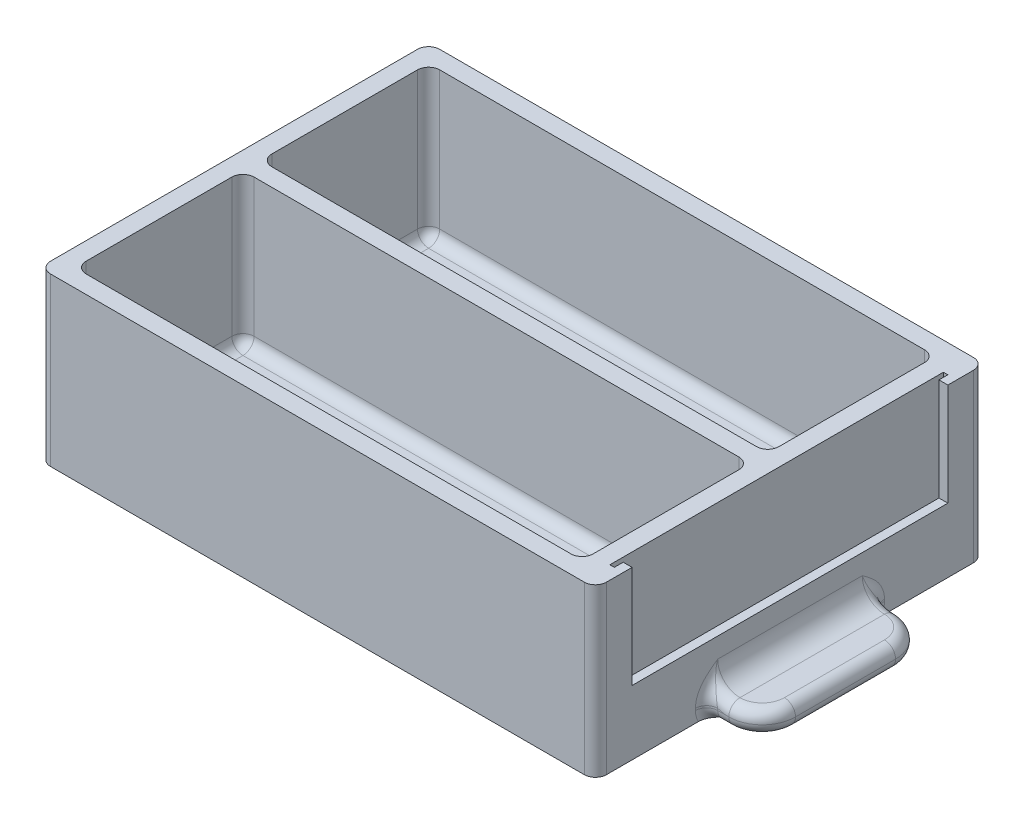
SolidWorks part; units mm, degrees
ref_plane "Спереди" through (0, 0, 0) normal (0, 0, 1) x (1, 0, 0)
ref_plane "Сверху" through (0, 0, 0) normal (0, 1, 0) x (1, 0, 0)
ref_plane "Справа" through (0, 0, 0) normal (1, 0, 0) x (0, 0, -1)
sketch "Эскиз1" plane through (0, 0, 0) normal (0, 1, 0) x (1, 0, 0)
  line L1 (-25, -17.5) -> (25, -17.5)
  line L2 (-25, -17.5) -> (-25, 17.5)
  line L3 (-25, 17.5) -> (25, 17.5)
  line L4 (25, -17.5) -> (25, 17.5)
  line L5 (-25, -17.5) -> (25, 17.5) construction
  line L6 (-25, 17.5) -> (25, -17.5) construction
  line L7 (-23.4, 15.9) -> (22.2, 15.9)
  line L8 (-23.4, 15.9) -> (-23.4, -15.9)
  line L9 (-23.4, -15.9) -> (22.2, -15.9)
  line L10 (22.2, 15.9) -> (22.2, -15.9)
  line L11 (-23.4, -0.8) -> (22.2, -0.8)
  line L12 (-23.4, -0.8) -> (-23.4, 0.8)
  line L13 (-23.4, 0.8) -> (22.2, 0.8)
  line L14 (22.2, -0.8) -> (22.2, 0.8)
  line L15 (-23.4, -0.8) -> (22.2, 0.8) construction
  line L16 (-23.4, 0.8) -> (22.2, -0.8) construction
  point P0 (0, 0)
  point P10 (-0.6, 0)
  dimension "D1" = 50
  dimension "D2" = 35
  dimension "D3" = 1.6
  dimension "D4" = 1.6
  dimension "D5" = 1.6
  dimension "D6" = 2.8
  dimension "D7" = 1.6
extrude "Бобышка-Вытянуть1" add sketch "Эскиз1" along normal blind 15 contours L1 L4 L3 L2
extrude "Вырез-Вытянуть1" cut sketch "Эскиз1<3>" along normal through all from offset 1.6 contours L11 L8 L9 L10 | L8 L13 L10 L7 region at (-0.6, 0, -8.35) region at (-0.6, 0, 8.35)
sketch "Эскиз1<3>" plane through (0, 0, 0) normal (0, 1, 0) x (1, 0, 0) same geometry as "Эскиз1"
sketch "Эскиз2" plane through (25, 0, 0) normal (1, 0, 0) x (0, 0, -1)
  line L0 (-17.5, 15) -> (17.5, 15) construction
  line L1 (-15, 5) -> (15, 5)
  line L2 (-15, 5) -> (-15, 15)
  line L3 (-15, 15) -> (15, 15)
  line L4 (15, 5) -> (15, 15)
  line L5 (-15, 5) -> (15, 15) construction
  line L6 (-15, 15) -> (15, 5) construction
  line L8 (-14.2, 5.8) -> (14.2, 5.8)
  line L9 (-14.2, 5.8) -> (-14.2, 15)
  line L10 (-14.2, 15) -> (14.2, 15)
  line L11 (14.2, 5.8) -> (14.2, 15)
  line L12 (-14.2, 5.8) -> (14.2, 15) construction
  line L13 (-14.2, 15) -> (14.2, 5.8) construction
  point P0 (0, 10)
  point P7 (0, 10.4)
  dimension "D1" = 30
  dimension "D2" = 10
  dimension "D3" = 0.8
  dimension "D4" = 0.8
extrude "Вырез-Вытянуть2" cut sketch "Эскиз2" against normal blind 0.4 from offset 0.8 contours L2 L3 L4 L1 offset against normal yes
extrude "Вырез-Вытянуть3" cut sketch "Эскиз2<3>" against normal blind 0.8 contours L8 L11 L10 L9
sketch "Эскиз2<3>" plane through (25, 0, 0) normal (1, 0, 0) x (0, 0, -1) same geometry as "Эскиз2"
sketch "Эскиз3" plane through (0, 0, 0) normal (0, 0, 1) x (1, 0, 0)
  line L0 (25, 0) -> (25, 4)
  line L1 (25, 0) -> (30, 0)
  line L2 (30, 0) -> (30, 2)
  line L3 (30, 2) -> (27, 2)
  arc A0 (25, 4) -> (27, 2) centre (27, 4) ccw
  dimension "D3" = 2
  dimension "D1" = 5
  dimension "D2" = 2
extrude "Бобышка-Вытянуть2" add sketch "Эскиз3" along normal mid plane 15
fillet "Скругление1" radius 3 2 edges at (30, 1, -7.5) (30, 1, 7.5)
fillet "Скругление2" radius 1 10 edges at (25.5858, 2.5858, -7.5) (26, 0, -7.5) (29.1213, 0, -6.6213) (29.1213, 2, -6.6213) (26, 0, 7.5) (25.5858, 2.5858, 7.5) (29.1213, 2, 6.6213) (29.1213, 0, 6.6213) (30, 0, 0) (30, 2, 0) tangent propagation no
fillet "Скругление3" radius 1 6 edges at (25, 2.4562, -7.3808) (25, 0.2929, -7.2071) (25, 2.4562, 7.3808) (25, 0.2929, 7.2071) (25, 1.382, -7.5) (25, 1.382, 7.5)
fillet "Скругление4" radius 1 16 edges at (22.2, 8.3, 15.9) (22.2, 8.3, -15.9) (-23.4, 8.3, 15.9) (-23.4, 8.3, -15.9) (22.2, 1.6, -8.35) (-0.6, 1.6, -15.9) (-23.4, 1.6, -8.35) (22.2, 1.6, 8.35) (-0.6, 1.6, -0.8) (-0.6, 1.6, 0.8) (-23.4, 1.6, 8.35) (-0.6, 1.6, 15.9) (22.2, 8.3, 0.8) (22.2, 8.3, -0.8) (-23.4, 8.3, 0.8) (-23.4, 8.3, -0.8)
fillet "Скругление5" radius 1 4 edges at (25, 7.5, -17.5) (-25, 7.5, -17.5) (-25, 7.5, 17.5) (25, 7.5, 17.5)
equation "\"D6@Эскиз1\"=1.6+0.4+0.8"
